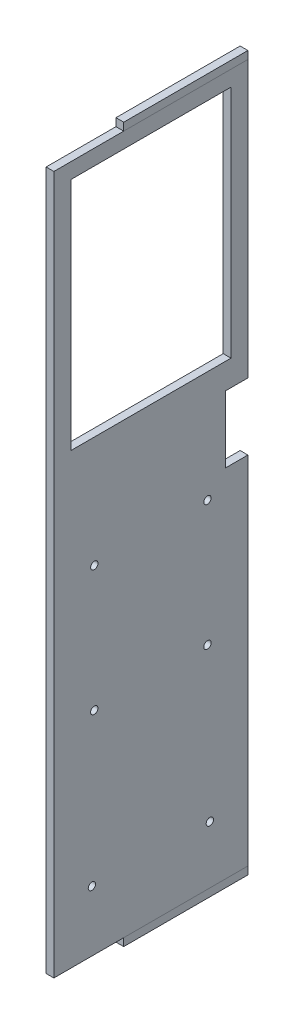
SolidWorks part; units mm, degrees
ref_plane "Front Plane" through (0, 0, 0) normal (0, 0, 1) x (1, 0, 0)
ref_plane "Top Plane" through (0, 0, 0) normal (0, 1, 0) x (1, 0, 0)
ref_plane "Right Plane" through (0, 0, 0) normal (1, 0, 0) x (0, 0, -1)
sketch "Sketch1" plane through (0, 0, 0) normal (1, 0, 0) x (0, 0, -1)
  line L1 (0, 0) -> (79.375, 0)
  line L2 (0, 0) -> (0, 285.75)
  line L3 (0, 285.75) -> (79.375, 285.75)
  line L4 (79.375, 0) -> (79.375, 285.75)
  dimension "D1" = 79.375
  dimension "D2" = 285.75
extrude "Boss-Extrude1" add sketch "Sketch1" along normal blind 3.175
ref_plane "Plane1" through (0, 0, -39.6875) normal (0, 0, -1) x (-1, 0, 0)
sketch "Sketch2" plane through (0, 0, 0) normal (-1, 0, 0) x (0, 0, 1)
  line L1 (-72.4535, 183.388) -> (-6.9215, 183.388)
  line L2 (-72.4535, 183.388) -> (-72.4535, 279.4)
  line L3 (-72.4535, 279.4) -> (-6.9215, 279.4)
  line L4 (-6.9215, 183.388) -> (-6.9215, 279.4)
  line L6 (-79.375, 285.75) -> (0, 285.75) construction
  point P6 (-39.6875, 285.75)
  point P7 (-39.6875, 279.4)
  dimension "D1" = 96.012
  dimension "D2" = 65.532
  dimension "D3" = 6.35
extrude "Cut-Extrude1" cut sketch "Sketch2" against normal up to next
sketch "Sketch3" plane through (0, 0, 0) normal (-1, 0, 0) x (0, 0, 1)
  line L0 (-79.375, 0) -> (-79.375, 285.75) construction
  line L1 (-79.375, 145.605) -> (-70.1675, 145.605)
  line L2 (-79.375, 145.605) -> (-79.375, 172.905)
  line L3 (-79.375, 172.905) -> (-70.1675, 172.905)
  line L4 (-70.1675, 145.605) -> (-70.1675, 172.905)
  line L5 (-65.8175, 172.905) -> (-61.6175, 172.905) construction
  line L6 (-61.6175, 145.605) -> (-59.1175, 145.605) construction
  line L7 (-70.1675, 159.005) -> (-70.1675, 156.505) construction
extrude "Cut-Extrude2" cut sketch "Sketch3" against normal up to next
hole_wizard "Ø3.0mm Dowel Hole1" positions "Sketch4" profile "Sketch5" hole size "Ø3.0" standard "ANSI Metric" end condition up to next
sketch "Sketch4" plane through (0, 0, 0) normal (-1, 0, 0) x (0, 0, 1)
  point P0 (-63.8175, 23.495)
  point P3 (-15.5575, 24.765)
  point P6 (-16.5375, 86.605)
  point P9 (-62.8375, 86.605)
  point P12 (-62.8375, 137.905)
  point P15 (-16.5375, 137.905)
sketch "Sketch5" plane through (0, 23.495, -63.8175) normal (0, 1, 0) x (0, 0, 1)
  line L0 (0, 0) -> (0, 3.175)
  line L1 (0, 3.175) -> (1.5, 3.175)
  line L2 (1.5, 3.175) -> (1.5, 0)
  line L5 (1.5, 0) -> (0, 0)
  line L11 (0, -6.35) -> (0, 107.95) construction
  dimension "Thru Hole Dia." = 3
  dimension "Thru Hole Depth" = 3.175
sketch "Sketch7" plane through (3.175, 0, 0) normal (1, 0, 0) x (0, 0, -1)
  line L1 (79.375, 0) -> (28.575, 0)
  line L2 (79.375, 0) -> (79.375, -3.175)
  line L3 (79.375, -3.175) -> (28.575, -3.175)
  line L4 (28.575, 0) -> (28.575, -3.175)
  line L6 (79.375, 285.75) -> (28.575, 285.75)
  line L7 (79.375, 285.75) -> (79.375, 288.925)
  line L8 (79.375, 288.925) -> (28.575, 288.925)
  line L9 (28.575, 285.75) -> (28.575, 288.925)
  dimension "D1" = 3.175
  dimension "D2" = 3.175
  dimension "D3" = 50.8
extrude "Boss-Extrude2" add sketch "Sketch7" against normal blind 3.175 separate body
